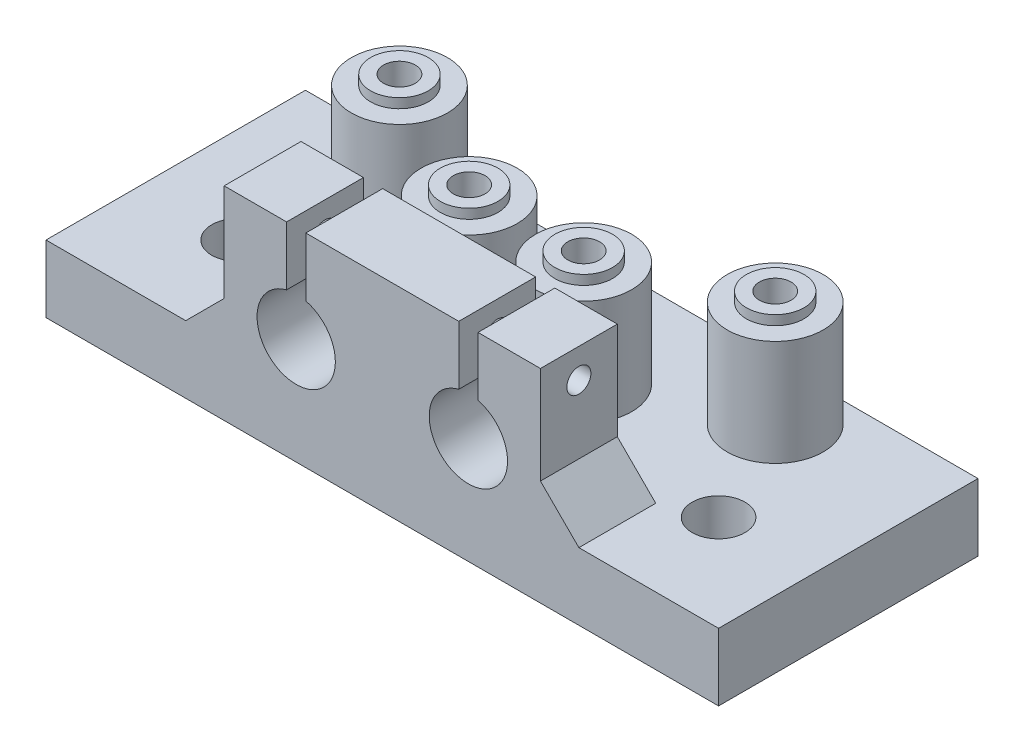
SolidWorks part; units mm, degrees
ref_plane "Front Plane" through (0, 0, 0) normal (0, 0, 1) x (1, 0, 0)
ref_plane "Top Plane" through (0, 0, 0) normal (0, 1, 0) x (1, 0, 0)
ref_plane "Right Plane" through (0, 0, 0) normal (1, 0, 0) x (0, 0, -1)
sketch "Sketch1" plane through (0, 0, 0) normal (0, 1, 0) x (1, 0, 0)
  line L0 (-5.96, 5) -> (5.96, 5) construction
  line L1 (19.75, 10) -> (-19.75, 10) construction
  line L2 (19.75, 10) -> (19.75, -10)
  line L3 (19.75, -10) -> (-19.75, -10)
  line L4 (-19.75, 10) -> (-19.75, -10)
  line L5 (0, -10) -> (0, 10) construction
  line L6 (19.75, 0) -> (-19.75, 0) construction
  line L7 (-5.96, 5) -> (-19.5546, 11.3393) construction
  line L8 (5.96, 5) -> (19.5546, 11.3393) construction
  line L9 (-19.75, 10) -> (-19.75, 17)
  line L10 (-19.75, 17) -> (19.75, 17)
  line L11 (19.75, 17) -> (19.75, 10)
  point P0 (0, 0)
  point P6 (0, 5)
  dimension "D1" = 20
  dimension "D2" = 39.5
  dimension "D3" = 11.92
  dimension "D4" = 5
  dimension "D5" = 15
  dimension "D6" = 7
  dimension "D7" = 25
extrude "Boss-Extrude1" add sketch "Sketch1" along normal blind 3
sketch "Sketch4" plane through (0, 0, 10) normal (0, 0, 1) x (1, 0, 0)
  line L0 (-19.75, 3) -> (19.75, 3) construction
  line L1 (1.46, 3) -> (16.46, 3)
  line L2 (1.46, 3) -> (1.46, 17.15)
  line L3 (1.46, 17.15) -> (16.46, 17.15)
  line L4 (16.46, 3) -> (16.46, 17.15)
  line L5 (8.96, 17.15) -> (8.96, 3) construction
  line L6 (1.46, 10.075) -> (16.46, 10.075) construction
  line L8 (7.96, 17.15) -> (9.96, 17.15)
  line L9 (7.96, 17.15) -> (7.96, 7.075)
  line L10 (7.96, 7.075) -> (9.96, 7.075)
  line L11 (9.96, 17.15) -> (9.96, 7.075)
  line L12 (8.96, 7.075) -> (8.96, 17.15) construction
  line L13 (7.96, 12.1125) -> (9.96, 12.1125) construction
  circle A0 centre (8.96, 7.075) radius 4.075
  point P208 (8.96, 12.1125)
  point P268 (8.96, 10.075)
  line M6 (19.75, 3) -> (-19.75, 3)
  dimension "D2" = 8.15
  dimension "D4" = 6
  dimension "D1" = 15
  dimension "D3" = 2
  dimension "D5" = 3
extrude "Boss-Extrude2" add sketch "Sketch4" against normal blind 8 contours A0 L9 L3 L2 L1 | A0 L4 L3 L11 M6 region at (4.2326, 10.8015, 10) region at (13.6874, 10.8015, 10)
chamfer "Chamfer1" distance 4 angle 45 1 edges at (16.46, 3, 6)
hole_wizard "M3x0.5 Tapped Hole1" positions "Sketch5" profile "Sketch6" tap size "M3x0.5" standard "ANSI Metric" end condition through all
sketch "Sketch5" plane through (1.46, 0, 0) normal (-1, 0, 0) x (0, 0, 1)
  line L0 (2, 14.0877) -> (6, 14.0877) construction
  line L1 (2, 3) -> (2, 17.15) construction
  line L2 (6, 14.0877) -> (6, 17.15) construction
  line L3 (2, 17.15) -> (10, 17.15) construction
  line L5 (2, 17.15) -> (2, 11.0254) construction
  point P0 (6, 14.0877)
sketch "Sketch6" plane through (1.46, 14.0877, 6) normal (0, 1, 0) x (0, 0, 1)
  line L0 (0, 0) -> (0, 18.29)
  line L1 (0, 18.29) -> (1.25, 18.29)
  line L2 (1.25, 18.29) -> (1.25, 0)
  line L5 (1.25, 0) -> (0, 0)
  line L11 (0, -6.35) -> (0, 107.95) construction
  dimension "Thru Tap Drill Dia." = 2.5
  dimension "Thru Tap Drill Depth" = 18.29
cosmetic thread "Hole Thread13" parameters "D2"=3
mirror "Mirror1" about plane through (0, 0, 0) normal (1, 0, 0) of "M3x0.5 Tapped Hole1", "Chamfer1", "Boss-Extrude2"
cosmetic thread "Hole Thread14" parameters "D2"=3
sketch "Sketch7" plane through (-1.46, 0, 0) normal (1, 0, 0) x (0, 0, -1)
  line L4 (-10, 17.15) -> (-10, 3)
  line L5 (-10, 3) -> (-2, 3)
  line L6 (-2, 3) -> (-2, 17.15)
  line L7 (-2, 17.15) -> (-10, 17.15)
  line L8 (-10, 17.15) -> (-10, 3)
  line L9 (-10, 3) -> (-2, 3)
  line L10 (-2, 3) -> (-2, 17.15)
  line L11 (-2, 17.15) -> (-10, 17.15)
  circle A0 centre (-6, 14.0877) radius 1.25 construction
  circle A1 centre (-6, 14.0877) radius 1.25
  dimension "D1" = 0
extrude "Boss-Extrude3" add sketch "Sketch7" along normal up to next
sketch "Sketch8" plane through (0, 3, 0) normal (0, 1, 0) x (1, 0, 0)
  circle A0 centre (-5.96, 5) radius 5
  circle A1 centre (5.96, 5) radius 5
  circle A2 centre (-19.5546, 11.3393) radius 5
  circle A3 centre (19.5546, 11.3393) radius 5
  dimension "D1" = 10
extrude "Boss-Extrude4" add sketch "Sketch8" along normal blind 12
sketch "Sketch9" plane through (0, 15, 0) normal (0, 1, 0) x (1, 0, 0)
  circle A0 centre (5.96, 5) radius 5 construction
  circle A1 centre (-5.96, 5) radius 5 construction
  circle A2 centre (5.96, 5) radius 5
  circle A3 centre (-5.96, 5) radius 5
  circle A4 centre (-5.96, 5) radius 3
  circle A5 centre (5.96, 5) radius 3
  circle A6 centre (-19.5546, 11.3393) radius 3
  circle A7 centre (-19.5546, 11.3393) radius 5
  circle A8 centre (19.5546, 11.3393) radius 3
  circle A9 centre (19.5546, 11.3393) radius 5
  dimension "D1" = 6
extrude "Cut-Extrude1" cut sketch "Sketch9" against normal blind 1
sketch "Sketch12" plane through (0, 0, 0) normal (0, -1, 0) x (1, 0, 0)
  line L1 (-19.75, -17) -> (-35, -17)
  line L2 (-19.75, -17) -> (-19.75, 10)
  line L3 (-19.75, 10) -> (-35, 10)
  line L4 (-35, -17) -> (-35, 10)
  line L5 (-27.375, 10) -> (-27.375, -17) construction
  line L6 (-19.75, -3.5) -> (-35, -3.5) construction
  line L7 (19.75, -17) -> (35, -17)
  line L8 (19.75, -17) -> (19.75, 10)
  line L9 (19.75, 10) -> (35, 10)
  line L10 (35, -17) -> (35, 10)
  line L11 (27.375, 10) -> (27.375, -17) construction
  line L12 (19.75, -3.5) -> (35, -3.5) construction
  point P132 (-27.375, -3.5)
  point P166 (27.375, -3.5)
  dimension "D2" = 70
extrude "Boss-Extrude5" add sketch "Sketch12" against normal up to surface (3 mm away) up to face at (0, 3, -7.1357)
hole_wizard "M4x0.7 Tapped Hole1" positions "Sketch2" profile "Sketch3" tap size "M4x0.7" standard "ANSI Metric" end condition through all
sketch "Sketch2" plane through (0, 0, 0) normal (0, 1, 0) x (1, 0, 0)
  line L0 (8.96, -2) -> (8.96, 5) construction
  line L1 (8.96, 5) -> (5.96, 5) construction
  point P0 (-5.96, 5)
  point P2 (5.96, 5)
  point P11 (-19.5546, 11.3393)
  point P14 (19.5546, 11.3393)
  dimension "D1" = 11.92
  dimension "D2" = 5
  dimension "D3" = 3
sketch "Sketch3" plane through (-5.96, 0, -5) normal (1, 0, 0) x (0, 0, -1)
  line L0 (0, 0) -> (0, 17.15)
  line L1 (0, 17.15) -> (1.65, 17.15)
  line L2 (1.65, 17.15) -> (1.65, 0)
  line L5 (1.65, 0) -> (0, 0)
  line L11 (0, -6.35) -> (0, 107.95) construction
  dimension "Thru Tap Drill Dia." = 3.3
  dimension "Thru Tap Drill Depth" = 17.15
cosmetic thread "Hole Thread1" parameters "D2"=4
cosmetic thread "Hole Thread2" parameters "D2"=4
cosmetic thread "Hole Thread11" parameters "D2"=4
cosmetic thread "Hole Thread12" parameters "D2"=4
hole_wizard "M5 Clearance Hole3" positions "Sketch10" profile "Sketch11" hole size "M5" standard "ANSI Metric" end condition through all
sketch "Sketch10" plane through (0, 3, 0) normal (0, 1, 0) x (1, 0, 0)
  line L0 (-25, 0) -> (25, 0) construction
  circle A0 centre (-25, 0) radius 4.5
  point P6 (-25, 0)
  point P12 (25, 0)
  dimension "D2" = 9
  dimension "D1" = 50
sketch "Sketch11" plane through (25, 3, 0) normal (1, 0, 0) x (0, 0, 1)
  line L0 (0, 0) -> (0, 3)
  line L1 (0, 3) -> (2.75, 3)
  line L2 (2.75, 3) -> (2.75, 0)
  line L5 (2.75, 0) -> (0, 0)
  line L11 (0, -6.35) -> (0, 107.95) construction
  dimension "Thru Hole Dia." = 5.5
  dimension "Thru Hole Depth" = 3
other "DeleteFace1" face at (19.75, 3.355, 6) face at (-19.75, 3.355, 6) and patch yes
other "Move Face1" face at (-25, 0, 2.75) offset 4 parameters "D1"=4
